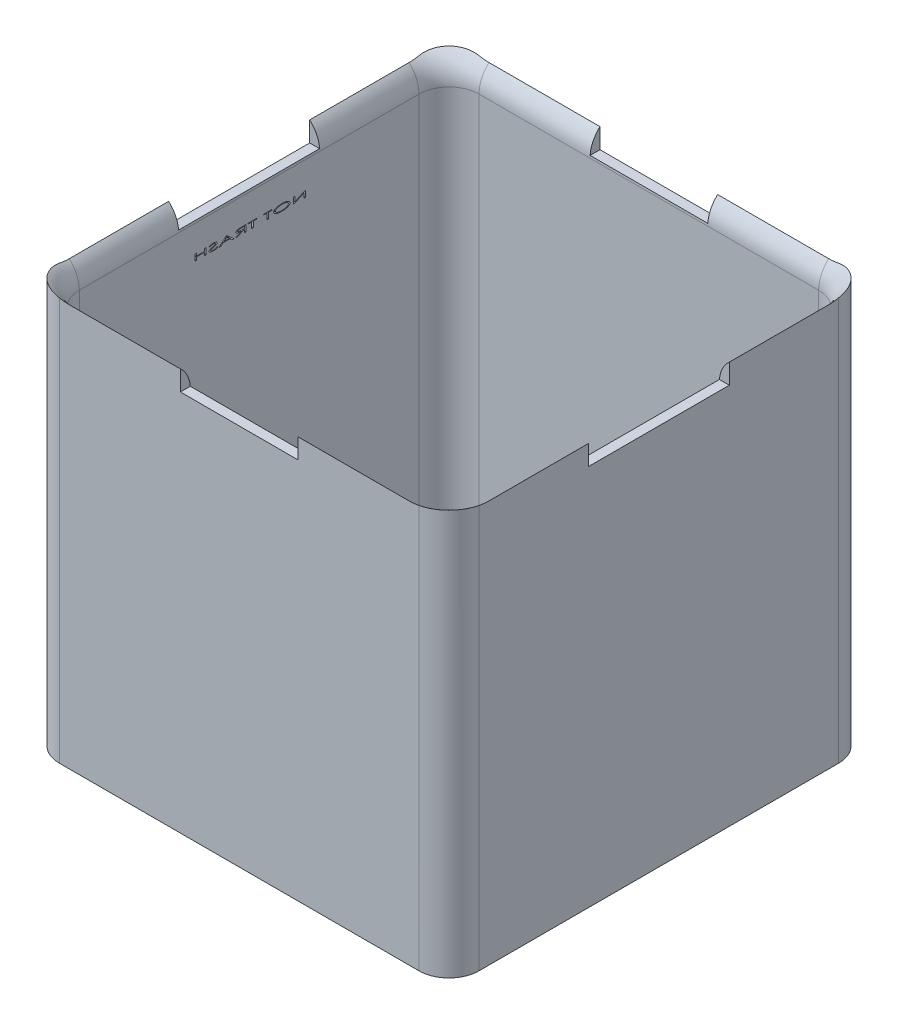
SolidWorks part; units mm, degrees
ref_plane "Front Plane" through (0, 0, 0) normal (0, 0, 1) x (1, 0, 0)
ref_plane "Top Plane" through (0, 0, 0) normal (0, 1, 0) x (1, 0, 0)
ref_plane "Right Plane" through (0, 0, 0) normal (1, 0, 0) x (0, 0, -1)
sketch "Sketch1" plane through (0, 0, 0) normal (0, 1, 0) x (1, 0, 0)
  line L0 (-75.9007, -93.2217) -> (-70.9007, -88.2217)
  line L1 (-70.9007, 111.7783) -> (129.0993, 111.7783)
  line L2 (-70.9007, 111.7783) -> (-70.9007, -88.2217)
  line L3 (-70.9007, -88.2217) -> (129.0993, -88.2217)
  line L4 (129.0993, 111.7783) -> (129.0993, -88.2217)
  line L5 (-75.9007, 116.7783) -> (134.0993, 116.7783)
  line L6 (-75.9007, 116.7783) -> (-75.9007, -93.2217)
  line L7 (-75.9007, -93.2217) -> (134.0993, -93.2217)
  line L8 (134.0993, 116.7783) -> (134.0993, -93.2217)
  line L9 (134.0993, -93.2217) -> (129.0993, -88.2217)
  line L10 (-75.9007, 116.7783) -> (-70.9007, 111.7783)
  dimension "D1" = 200
  dimension "D2" = 200
  dimension "D3" = 210
  dimension "D4" = 210
extrude "Boss-Extrude1" add sketch "Sketch1" along normal blind 5 contours L10 L6 L0 L2 | L7 L9 L3 L0 | L5 L10 L1 L4 L9 L8 | L4 L1 L2 L3 region at (-73.421, 0, -11.7783) region at (29.0993, 0, 90.742) region at (29.0993, 0, -11.7783) region at (29.0993, 0, -113.8084)
extrude "Boss-Extrude2" add sketch "Sketch1<3>" along normal blind 205 contours L10 L6 L0 L2 | L5 L10 L1 L4 L9 L8 | L7 L9 L3 L0 region at (-73.421, 0, -11.7783) region at (29.0993, 0, 90.742) region at (29.0993, 0, -113.8084)
sketch "Sketch1<3>" plane through (0, 0, 0) normal (0, 1, 0) x (1, 0, 0) same geometry as "Sketch1"
fillet "Fillet1" radius 15 8 edges at (134.0993, 102.5, 93.2217) (-70.9007, 105, 88.2217) (-75.9007, 102.5, 93.2217) (129.0993, 105, 88.2217) (129.0993, 105, -111.7783) (134.0993, 102.5, -116.7783) (-70.9007, 105, -111.7783) (-75.9007, 102.5, -116.7783)
fillet "Fillet2" radius 15 8 edges at (-66.5073, 205, -107.3849) (29.0993, 205, -111.7783) (124.7059, 205, -107.3849) (129.0993, 205, -11.7783) (124.7059, 205, 83.8283) (29.0993, 205, 88.2217) (-66.5073, 205, 83.8283) (-70.9007, 205, -11.7783)
sketch "Sketch3" plane through (-75.9007, 0, 0) normal (-1, 0, 0) x (0, 0, 1)
  text T0 "NOT TRASH" font "Century Gothic" height 3.175
  point P1 (0, 0)
extrude "Cut-Extrude1" cut sketch "Sketch3" against normal blind 59
sketch "Sketch5" plane through (134.0993, 0, 0) normal (1, 0, 0) x (0, 0, -1)
  line L0 (96.7783, 201.1803) -> (-73.2217, 201.1803) construction
  line L1 (-23.5074, 201.1803) -> (47.0639, 201.1803)
  line L2 (-23.5074, 201.1803) -> (-23.5074, 191.1803)
  line L3 (-23.5074, 191.1803) -> (47.0639, 191.1803)
  line L4 (47.0639, 201.1803) -> (47.0639, 191.1803)
extrude "Cut-Extrude2" cut sketch "Sketch5" against normal blind 241
sketch "Sketch6" plane through (0, 0, -116.7783) normal (0, 0, -1) x (-1, 0, 0)
  line L0 (55.9007, 201.1803) -> (-114.0993, 201.1803) construction
  line L1 (-58.5419, 201.1803) -> (0.3433, 201.1803)
  line L2 (-58.5419, 201.1803) -> (-58.5419, 191.1803)
  line L3 (-58.5419, 191.1803) -> (0.3433, 191.1803)
  line L4 (0.3433, 201.1803) -> (0.3433, 191.1803)
extrude "Cut-Extrude3" cut sketch "Sketch6" against normal blind 241
